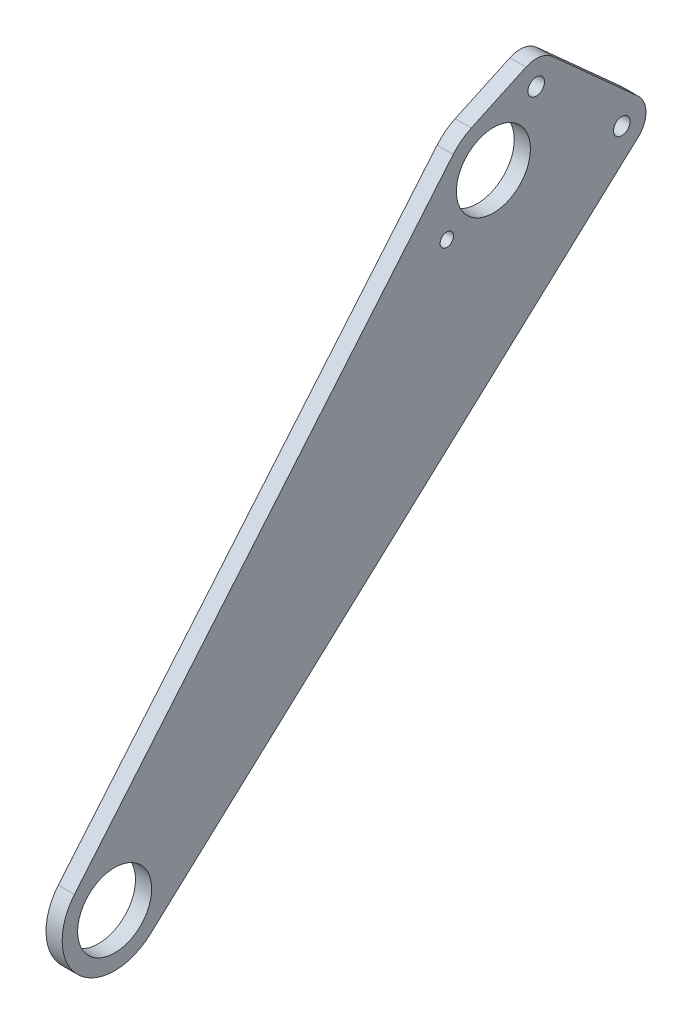
SolidWorks part; units mm, degrees
material "6061-T6 (SS)"
ref_plane "Front Plane" through (0, 0, 0) normal (0, 0, 1) x (1, 0, 0)
ref_plane "Top Plane" through (0, 0, 0) normal (0, 1, 0) x (1, 0, 0)
ref_plane "Right Plane" through (0, 0, 0) normal (1, 0, 0) x (0, 0, -1)
sketch "Sketch1" plane through (0, 0, 0) normal (1, 0, 0) x (0, 0, -1)
  line L0 (0, 0) -> (47.4141, 0) construction
  line L1 (0, 0) -> (143.6841, 143.6841) construction
  line L2 (143.6841, 143.6841) -> (148.964, 177.5652) construction
  line L3 (0, 0) -> (148.964, 177.5652) construction
  line L4 (0, 0) -> (199.4397, 167.3498) construction
  line L5 (148.964, 177.5652) -> (165.7989, 197.6325) construction
  line L6 (-15.8106, 13.2639) -> (133.1534, 190.8291)
  line L7 (140.2738, 196.2838) -> (161.7881, 206.2718)
  line L8 (172.1715, 204.7117) -> (205.8123, 174.429)
  line L9 (205.8681, 160.3212) -> (13.9282, -15.2286)
  line L10 (146.324, 160.6246) -> (130.6383, 163.069) construction
  circle A0 centre (0, 0) radius 14.5542
  circle A1 centre (143.6841, 143.6841) radius 14.5542 construction
  circle A2 centre (148.964, 177.5652) radius 14.5542
  circle A3 centre (199.4397, 167.3498) radius 3.2639
  circle A4 centre (165.7989, 197.6325) radius 3.2639
  arc A5 (172.1715, 204.7117) -> (161.7881, 206.2718) centre (165.7989, 197.6325) ccw
  arc A6 (205.8681, 160.3212) -> (205.8123, 174.429) centre (199.4397, 167.3498) ccw
  arc A7 (140.2738, 196.2838) -> (133.1534, 190.8291) centre (148.964, 177.5652) ccw
  arc A8 (13.9282, -15.2286) -> (-15.8106, 13.2639) centre (0, 0) cw
  circle A9 centre (130.6383, 163.069) radius 2.6289
  dimension "D1" = 29.1084
  dimension "D4" = 34.29
  dimension "D5" = 29.1084
  dimension "D6" = 29.1084
  dimension "D10" = 6.5278
  dimension "D12" = 6.5278
  dimension "D13" = 9.525
  dimension "D14" = 9.525
  dimension "D15" = 20.6375
  dimension "D16" = 20.6375
  dimension "D18" = 5.2578
  dimension "D2" = 45
  dimension "D3" = 203.2
  dimension "D7" = 231.775
  dimension "D8" = 260.35
  dimension "D9" = 40
  dimension "D11" = 26.1937
  dimension "D17" = 15.875
extrude "Boss-Extrude1" add sketch "Sketch1" along normal blind 6.35
